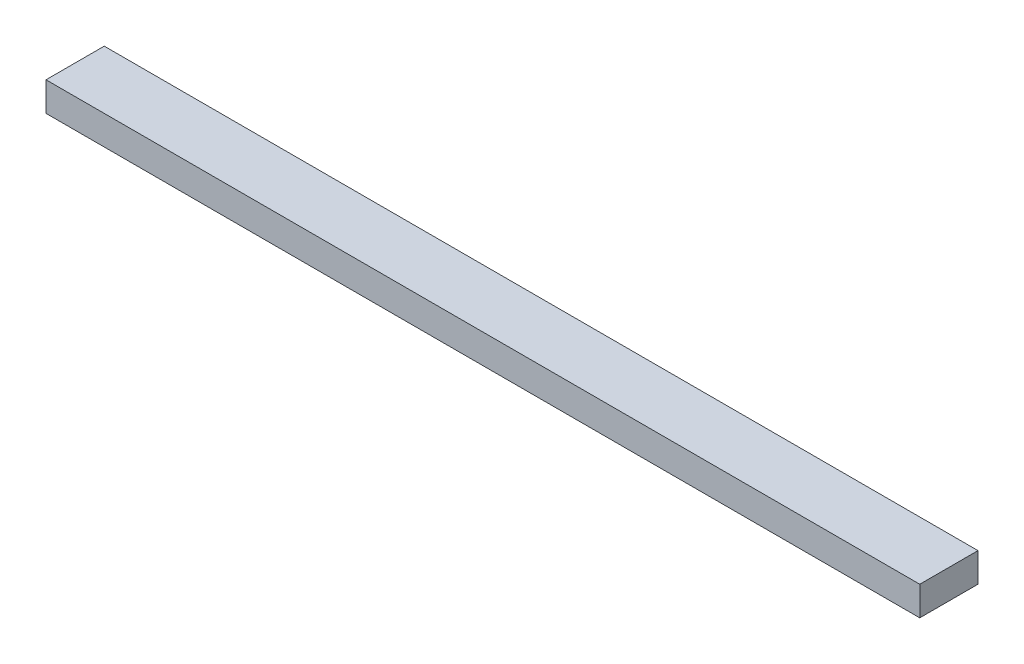
SolidWorks part; units mm, degrees
ref_plane "Front Plane" through (0, 0, 0) normal (0, 0, 1) x (1, 0, 0)
ref_plane "Top Plane" through (0, 0, 0) normal (0, 1, 0) x (1, 0, 0)
ref_plane "Right Plane" through (0, 0, 0) normal (1, 0, 0) x (0, 0, -1)
sketch "Sketch1" plane through (0, 0, 0) normal (0, 0, 1) x (1, 0, 0)
  line L0 (53.5799, -76.2) -> (-104.6669, -76.2) construction
  line L1 (90.6195, 6.35) -> (-139.3499, 6.35) construction
  line L2 (90.6195, -158.75) -> (-139.3499, -158.75) construction
  line L3 (90.6195, -152.4) -> (90.6195, 0) construction
  line L4 (65.2195, -14.2875) -> (-125.2805, -14.2875)
  line L5 (65.2195, -14.2875) -> (65.2195, -7.9375)
  line L6 (65.2195, -7.9375) -> (-125.2805, -7.9375)
  line L7 (-125.2805, -14.2875) -> (-125.2805, -7.9375)
  dimension "D1" = 6.35
  dimension "D2" = 123.825
  dimension "D3" = 190.5
  dimension "D4" = 25.4
extrude "Boss-Extrude1" add sketch "Sketch1" along normal blind 12.7
